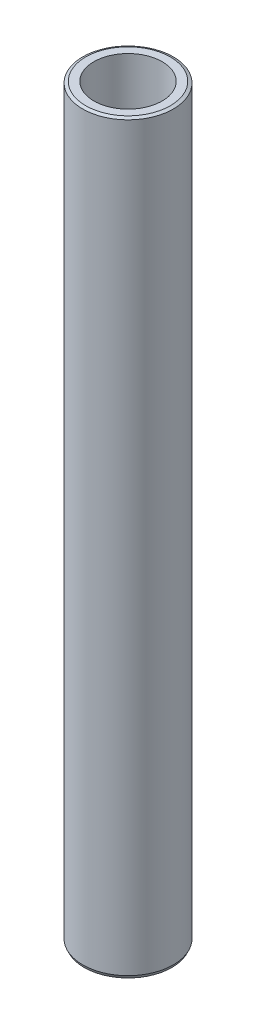
SolidWorks part; units mm, degrees
ref_plane "Front Plane" through (0, 0, 0) normal (0, 0, 1) x (1, 0, 0)
ref_plane "Top Plane" through (0, 0, 0) normal (0, 1, 0) x (1, 0, 0)
ref_plane "Right Plane" through (0, 0, 0) normal (1, 0, 0) x (0, 0, -1)
sketch "Sketch1" plane through (0, 0, 0) normal (0, 1, 0) x (1, 0, 0)
  circle A0 centre (0, 0) radius 15
  dimension "SHAFT_OD" = 30
extrude "Boss-Extrude1" add sketch "Sketch1" along normal blind 247.0863
sketch "Sketch2" plane through (0, 0, 0) normal (0, 1, 0) x (1, 0, 0)
  circle A0 centre (0, 0) radius 11.3057
  dimension "BORE_D" = 22.6114
extrude "Cut-Extrude1" cut sketch "Sketch2" along normal through all
chamfer "Chamfer1" distance 0.4552 angle 65.239 2 edges at (0, 247.0863, 15) (0, 0, 15) first distance on face at (0, 247.0863, 15) first distance on face at (0, 0, 11.3057)
